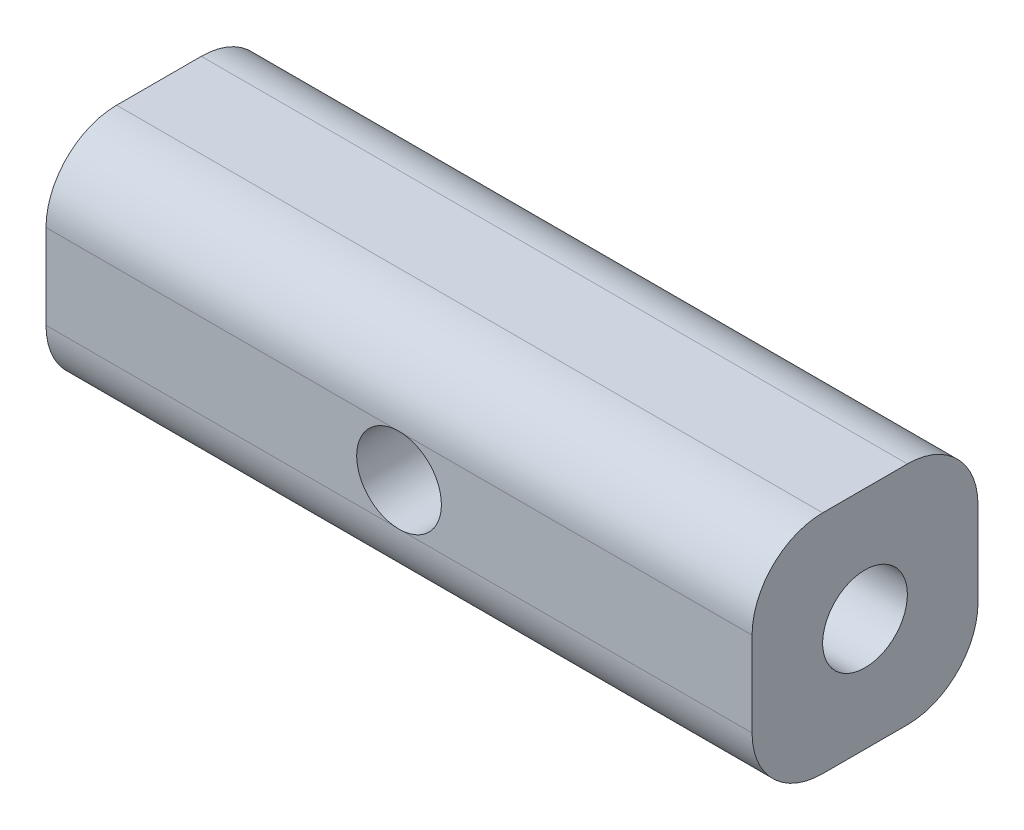
SolidWorks part; units mm, degrees
ref_plane "Plan de face" through (0, 0, 0) normal (0, 0, 1) x (1, 0, 0)
ref_plane "Plan de dessus" through (0, 0, 0) normal (0, 1, 0) x (1, 0, 0)
ref_plane "Plan de droite" through (0, 0, 0) normal (1, 0, 0) x (0, 0, -1)
sketch "Esquisse1" plane through (0, 0, 0) normal (0, 0, 1) x (1, 0, 0)
  line L1 (0, 0) -> (250, 0)
  line L2 (0, 0) -> (0, 80)
  line L3 (0, 80) -> (250, 80)
  line L4 (250, 0) -> (250, 80)
  dimension "D1" = 250
  dimension "D2" = 80
extrude "Boss.-Extru.1" add sketch "Esquisse1" along normal blind 80
sketch "Esquisse2" plane through (250, 0, 0) normal (1, 0, 0) x (0, 0, -1)
  line L0 (0, 80) -> (-80, 0) construction
  circle A0 centre (-40, 40) radius 15
  dimension "D1" = 30
extrude "Enlèv. mat.-Extru.1" cut sketch "Esquisse2" against normal through all
sketch "Esquisse3" plane through (0, 0, 80) normal (0, 0, 1) x (1, 0, 0)
  line L0 (0, 0) -> (250, 80) construction
  circle A0 centre (125, 40) radius 15
  dimension "D1" = 30
extrude "Enlèv. mat.-Extru.2" cut sketch "Esquisse3" against normal blind 80
fillet "Congé1" radius 25 4 edges at (125, 80, 0) (125, 0, 0) (125, 0, 80) (125, 80, 80)
